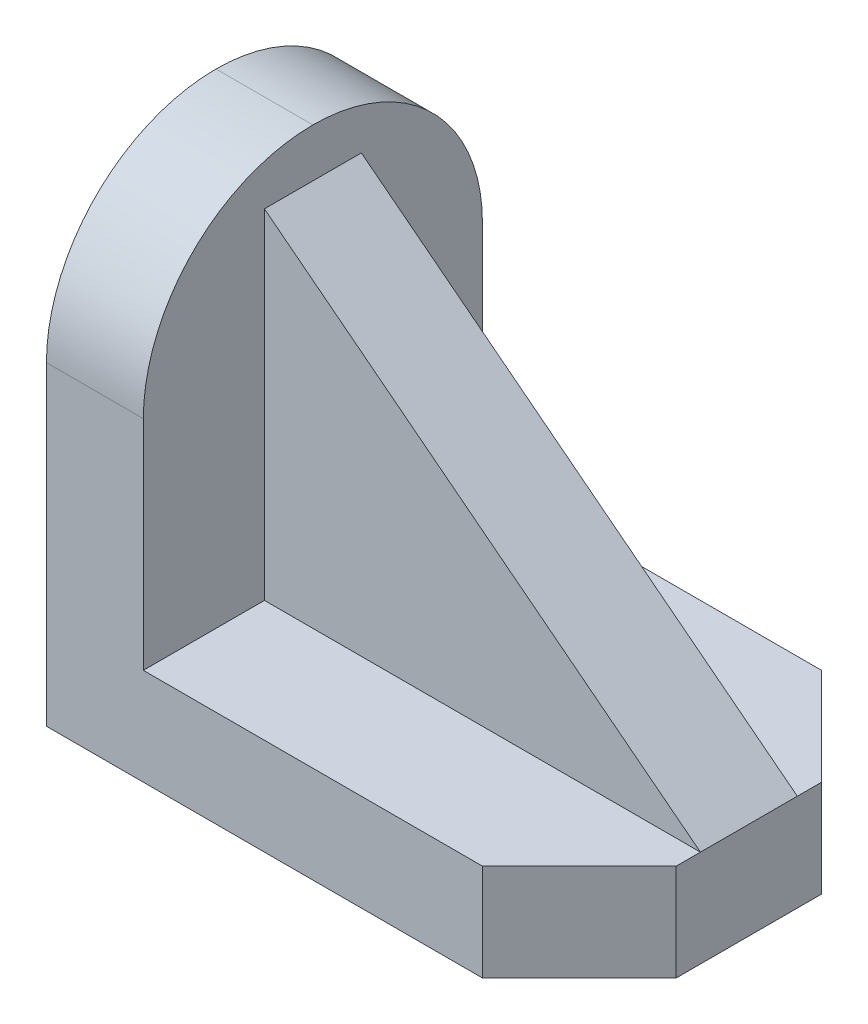
SolidWorks part; units mm, degrees
ref_plane "Front Plane" through (0, 0, 0) normal (0, 0, 1) x (1, 0, 0)
ref_plane "Top Plane" through (0, 0, 0) normal (0, 1, 0) x (1, 0, 0)
ref_plane "Right Plane" through (0, 0, 0) normal (1, 0, 0) x (0, 0, -1)
sketch "Sketch1" plane through (0, 0, 0) normal (0, 1, 0) x (1, 0, 0)
  line L1 (0, 0) -> (66, 0)
  line L2 (0, 0) -> (0, 42)
  line L3 (0, 42) -> (66, 42)
  line L4 (66, 0) -> (66, 42)
  dimension "D1" = 66
  dimension "D2" = 42
extrude "Boss-Extrude1" add sketch "Sketch1" along normal blind 12
chamfer "Chamfer1" distance 12 angle 45 1 edges at (66, 6, 0)
chamfer "Chamfer2" distance 12 angle 45 1 edges at (66, 6, -42)
sketch "Sketch2" plane through (0, 0, 0) normal (-1, 0, 0) x (0, 0, 1)
  line L1 (-42, 0) -> (0, 0)
  line L2 (-42, 0) -> (-42, 60)
  line L3 (-42, 60) -> (0, 60)
  line L4 (0, 0) -> (0, 60)
  dimension "D1" = 42
  dimension "D2" = 60
extrude "Boss-Extrude2" add sketch "Sketch2" against normal blind 12
fillet "Fillet1" radius 21 2 edges at (6, 60, -42) (6, 60, 0)
ref_plane "Plane1" through (0, 0, -21) normal (0, 0, 1) x (1, 0, 0)
sketch "Sketch4" plane through (0, 0, -21) normal (0, 0, 1) x (1, 0, 0)
  line L0 (12, 12) -> (12, 54)
  line L1 (12, 39) -> (12, 60) construction
  line L2 (12, 54) -> (66, 12)
  line L3 (54, 12) -> (66, 12) construction
  line L4 (66, 12) -> (12, 12)
  dimension "D1" = 42
  dimension "D2" = 54
extrude "Boss-Extrude4" add sketch "Sketch4" along normal mid plane 12
